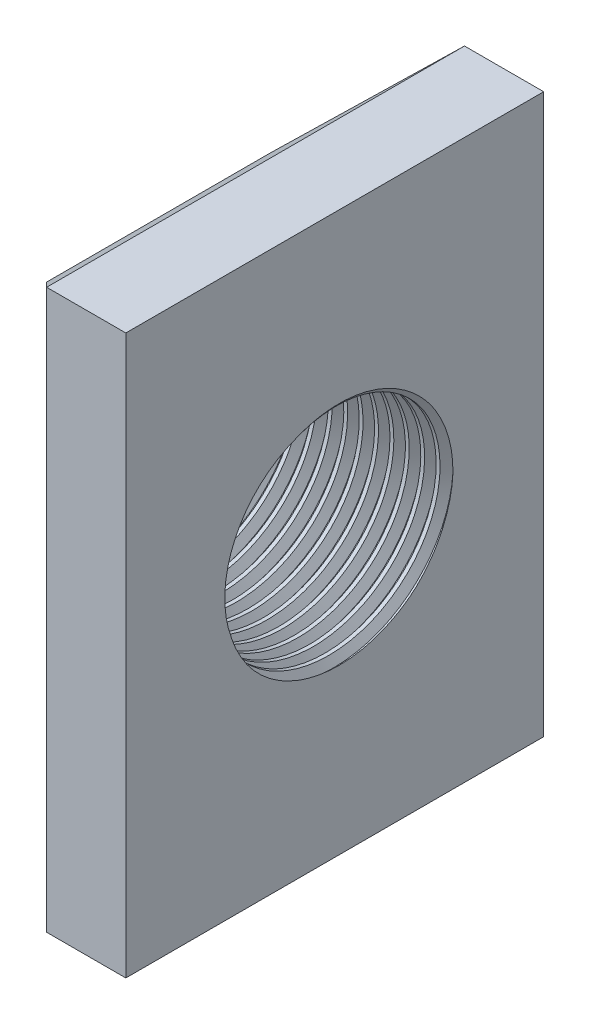
SolidWorks part; units mm, degrees
material "ABS"
ref_plane "Front Plane" through (0, 0, 0) normal (0, 0, 1) x (1, 0, 0)
ref_plane "Top Plane" through (0, 0, 0) normal (0, 1, 0) x (1, 0, 0)
ref_plane "Right Plane" through (0, 0, 0) normal (1, 0, 0) x (0, 0, -1)
sketch "Sketch1" plane through (0, 0, 0) normal (0, 0, 1) x (1, 0, 0)
  line L0 (0, -6.35) -> (0, 6.35)
  line L1 (0, 6.35) -> (-1.8, 6.35)
  line L2 (-1.8, 6.35) -> (-4.0071, 4.245)
  line L3 (-4.0071, 4.245) -> (-4.0071, -4.245)
  line L4 (-4.0071, -4.245) -> (-1.8, -6.35)
  line L5 (-1.8, -6.35) -> (0, -6.35)
  point P4 (0, 0)
  dimension "D1" = 12.7
  dimension "D2" = 8.49
  dimension "D3" = 3.05
  dimension "D4" = 1.8
extrude "Boss-Extrude1" add sketch "Sketch1" along normal mid plane 9.5
chamfer "Chamfer1" distance 2.2 angle 45 1 edges at (-4.0071, 0, 4.75)
chamfer "Chamfer2" distance 2.2 angle 45 1 edges at (-4.0071, 0, -4.75)
sketch "Sketch2" plane through (0, 0, 0) normal (1, 0, 0) x (0, 0, -1)
  circle A0 centre (0, 0) radius 2.5
  dimension "D1" = 5
extrude "Cut-Extrude1" cut sketch "Sketch2" against normal through all
thread "Thread1" pitch 0.35 method cut profile "Thread Profile1" start angle 0, offset 1, length 10, pitch 0.35, diameter 5
ref_plane "Plane1" through (-5.0071, 0, -2.5) normal (0, -1, 0) x (0, 0, -1)
sketch "Thread Profile1" plane through (-5.0071, 0, -2.5) normal (0, -1, 0) x (0, 0, -1)
  line L0 (0, 0) -> (0, 0.35) construction
  line L1 (0, 0) -> (0.1894, 0.1094)
  line L2 (0.1894, 0.1094) -> (0.1894, 0.1531)
  line L3 (0.1894, 0.1531) -> (0, 0.2625)
  line L4 (0.1894, 0.1312) -> (0, 0.1312) construction
  line L11 (0, 0) -> (0, 0.2625)
  point P2 (0, 0)
  dimension "Pitch" = 0.35
  dimension "Profile_Angle" = 60
  dimension "Profile_Land" = 0.0437
  dimension "Profile_Height" = 0.1894
